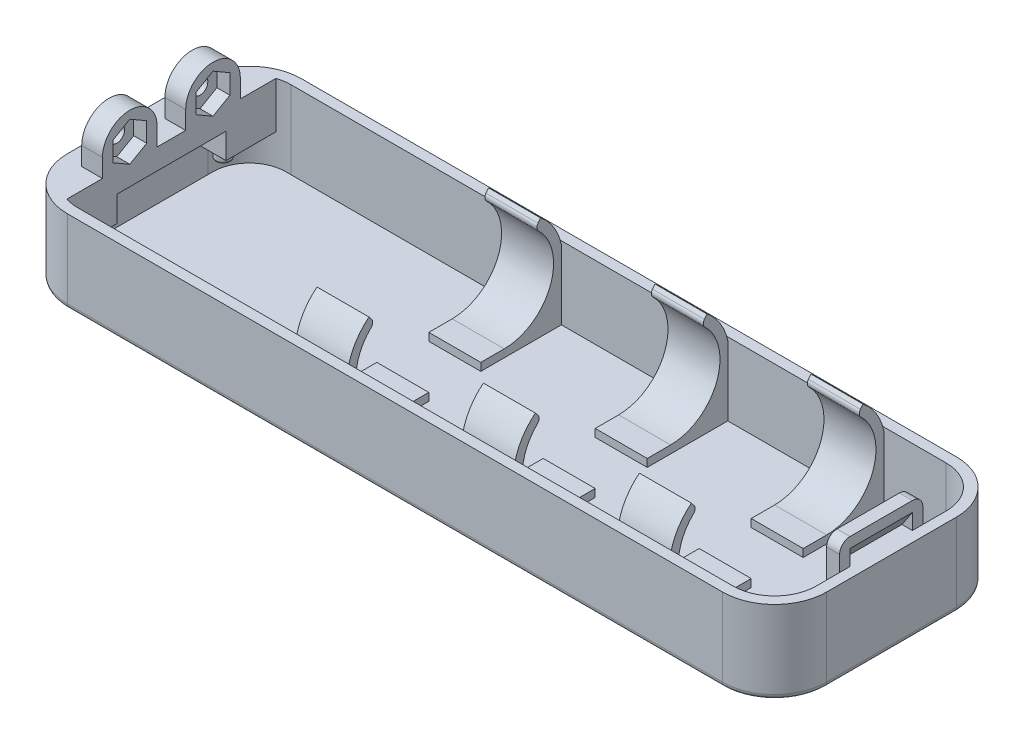
SolidWorks part; units mm, degrees
ref_plane "Front Plane" through (0, 0, 0) normal (0, 0, 1) x (1, 0, 0)
ref_plane "Top Plane" through (0, 0, 0) normal (0, 1, 0) x (1, 0, 0)
ref_plane "Right Plane" through (0, 0, 0) normal (1, 0, 0) x (0, 0, -1)
sketch "Sketch1" plane through (0, 0, 0) normal (0, 1, 0) x (1, 0, 0)
  line L1 (-10, 0) -> (-136, 0)
  line L2 (0, -10) -> (0, -35)
  line L3 (-10, -45) -> (-136, -45)
  line L4 (-146, -10) -> (-146, -35)
  arc A0 (-10, 0) -> (0, -10) centre (-10, -10) cw
  arc A1 (-10, -45) -> (0, -35) centre (-10, -35) ccw
  arc A2 (-146, -35) -> (-136, -45) centre (-136, -35) ccw
  arc A3 (-146, -10) -> (-136, 0) centre (-136, -10) cw
  point P7 (0, 0)
  point P10 (0, -45)
  point P15 (-146, 0)
  dimension "D3" = 10
  dimension "D1" = 146
  dimension "D2" = 45
extrude "Boss-Extrude1" add sketch "Sketch1" along normal blind 2
sketch "Sketch2" plane through (0, 2, 0) normal (0, 1, 0) x (1, 0, 0)
  line L4 (-10, 0) -> (-136, 0)
  line L5 (-146, -10) -> (-146, -35)
  line L6 (-136, -45) -> (-10, -45)
  line L7 (0, -35) -> (0, -10)
  line L8 (-10, 0) -> (-136, 0)
  line L9 (-146, -10) -> (-146, -35)
  line L10 (-136, -45) -> (-10, -45)
  line L11 (0, -35) -> (0, -10)
  line L20 (-10, -2) -> (-136, -2)
  line L21 (-144, -10) -> (-144, -35)
  line L22 (-136, -43) -> (-10, -43)
  line L23 (-2, -35) -> (-2, -10)
  line L24 (-10, -2) -> (-136, -2)
  line L25 (-144, -10) -> (-144, -35)
  line L26 (-136, -43) -> (-10, -43)
  line L27 (-2, -35) -> (-2, -10)
  arc A4 (0, -10) -> (-10, 0) centre (-10, -10) ccw
  arc A5 (-136, 0) -> (-146, -10) centre (-136, -10) ccw
  arc A6 (-146, -35) -> (-136, -45) centre (-136, -35) ccw
  arc A7 (-10, -45) -> (0, -35) centre (-10, -35) ccw
  arc A8 (0, -10) -> (-10, 0) centre (-10, -10) ccw
  arc A9 (-136, 0) -> (-146, -10) centre (-136, -10) ccw
  arc A10 (-146, -35) -> (-136, -45) centre (-136, -35) ccw
  arc A11 (-10, -45) -> (0, -35) centre (-10, -35) ccw
  arc A20 (-2, -10) -> (-10, -2) centre (-10, -10) ccw
  arc A21 (-136, -2) -> (-144, -10) centre (-136, -10) ccw
  arc A22 (-144, -35) -> (-136, -43) centre (-136, -35) ccw
  arc A23 (-10, -43) -> (-2, -35) centre (-10, -35) ccw
  arc A24 (-2, -10) -> (-10, -2) centre (-10, -10) ccw
  arc A25 (-136, -2) -> (-144, -10) centre (-136, -10) ccw
  arc A26 (-144, -35) -> (-136, -43) centre (-136, -35) ccw
  arc A27 (-10, -43) -> (-2, -35) centre (-10, -35) ccw
  dimension "D1" = 0
  dimension "D2" = 2
extrude "Boss-Extrude2" add sketch "Sketch2" along normal blind 14
fillet "Fillet1" radius 1 8 edges at (-73, 0, 0) (-143.0711, 0, 2.9289) (-146, 0, 22.5) (-143.0711, 0, 42.0711) (-73, 0, 45) (-2.9289, 0, 42.0711) (0, 0, 22.5) (-2.9289, 0, 2.9289)
sketch "Sketch3" plane through (0, 2, 0) normal (0, 1, 0) x (1, 0, 0)
  line L0 (-124, -2) -> (-124, -43)
  line L1 (-114, -2) -> (-114, -43)
  line L2 (-32, -2) -> (-32, -43)
  line L3 (-22, -2) -> (-22, -43)
  line L4 (-2, -35) -> (-2, -10)
  line L5 (-10, -2) -> (-136, -2)
  line L6 (-144, -10) -> (-144, -35)
  line L7 (-136, -43) -> (-10, -43)
  line L8 (-2, -35) -> (-2, -10)
  line L9 (-10, -2) -> (-136, -2)
  line L10 (-144, -10) -> (-144, -35)
  line L11 (-136, -43) -> (-10, -43)
  line L12 (-52, -43) -> (-52, -2)
  line L13 (-62, -43) -> (-62, -2)
  line L14 (-84, -43) -> (-84, -2)
  line L15 (-94, -43) -> (-94, -2)
  arc A4 (-2, -10) -> (-10, -2) centre (-10, -10) ccw
  arc A5 (-136, -2) -> (-144, -10) centre (-136, -10) ccw
  arc A6 (-144, -35) -> (-136, -43) centre (-136, -35) ccw
  arc A7 (-10, -43) -> (-2, -35) centre (-10, -35) ccw
  arc A8 (-2, -10) -> (-10, -2) centre (-10, -10) ccw
  arc A9 (-136, -2) -> (-144, -10) centre (-136, -10) ccw
  arc A10 (-144, -35) -> (-136, -43) centre (-136, -35) ccw
  arc A11 (-10, -43) -> (-2, -35) centre (-10, -35) ccw
  line M15 (-10, -2) -> (-136, -2)
  line M19 (-136, -43) -> (-10, -43)
  dimension "D2" = 10
  dimension "D3" = 10
  dimension "D5" = 20
  dimension "D6" = 20
  dimension "D4" = 10
  dimension "D7" = 10
  dimension "D8" = 20
  dimension "D9" = 20
extrude "Boss-Extrude3" add sketch "Sketch3" along normal blind 25 contours L13 L11 L12 L9 | L15 L11 L14 L9 | L3 L2 M15 M19 region at (-89, 2, 22.5) region at (-57, 2, 22.5) region at (-27, 2, 22.5)
ref_plane "Plane3" through (0, 12, 0) normal (0, 1, 0) x (1, 0, 0)
sketch "Sketch4" plane through (-22, 0, 0) normal (-1, 0, 0) x (0, 0, 1)
  line L2 (13, 13) -> (32, 13) construction
  line L3 (13, 22.5) -> (32, 22.5)
  line L4 (27.5, 3.5) -> (27.5, 2)
  line L5 (17.5, 3.5) -> (17.5, 2)
  line L8 (2, 3.5) -> (43, 3.5)
  line L9 (43, 3.5) -> (43, 15.3585)
  line L10 (43, 27) -> (2, 27)
  line L11 (2, 15.3585) -> (2, 3.5)
  line L12 (13, 3.5) -> (32, 3.5)
  line L13 (6, 21.807) -> (7.0889, 20.437)
  line L16 (43, 15.3585) -> (43, 27)
  line L19 (2, 27) -> (2, 15.3585)
  line L20 (39, 21.807) -> (37.9111, 20.437)
  line L21 (2, 2) -> (43, 2)
  line L22 (43, 2) -> (43, 16)
  line L23 (43, 16) -> (43, 27)
  line L24 (43, 27) -> (2, 27)
  line L25 (2, 27) -> (2, 16)
  line L26 (2, 16) -> (2, 2)
  line L27 (2, 2) -> (43, 2)
  line L28 (43, 2) -> (43, 16)
  line L29 (43, 16) -> (43, 27)
  line L30 (43, 27) -> (2, 27)
  line L31 (2, 27) -> (2, 16)
  line L32 (2, 16) -> (2, 2)
  arc A0 (13, 22.5) -> (13, 3.5) centre (13, 13) ccw
  arc A1 (32, 3.5) -> (32, 22.5) centre (32, 13) ccw
  arc A2 (2, 15.3585) -> (6, 21.807) centre (13, 13) cw
  arc A3 (43, 15.3585) -> (39, 21.807) centre (32, 13) ccw
  point P4 (22.5, 27)
  point P5 (22.5, 13)
  point P10 (22.5, 22.5)
  point P31 (22.5, 3.5)
  line M41 (43, 2) -> (2, 2)
  line M42 (2, 2) -> (2, 16)
  line M43 (2, 16) -> (2, 27)
  line M44 (2, 27) -> (43, 27)
  line M45 (43, 27) -> (43, 16)
  line M46 (43, 16) -> (43, 2)
  dimension "D2" = 19
  dimension "D3" = 19
  dimension "D4" = 4
  dimension "D5" = 4
  dimension "D6" = 1.5
  dimension "D7" = 1.75
  dimension "D8" = 10
  dimension "D9" = 5
sketch "Sketch7" plane through (0, 12, 0) normal (0, 1, 0) x (1, 0, 0)
  line L2 (-144, -10) -> (-144, -35)
  line L4 (-138.5, -2.4007) -> (-138.5, -42.5993)
  arc A0 (-136, -2) -> (-144, -10) centre (-136, -10) ccw construction
  arc A1 (-144, -35) -> (-136, -43) centre (-136, -35) ccw construction
  arc A2 (-136, -2) -> (-144, -10) centre (-136, -10) ccw
  arc A3 (-144, -35) -> (-136, -43) centre (-136, -35) ccw
  dimension "D3" = 5.5
extrude "Boss-Extrude5" add sketch "Sketch7" along normal offset from surface (12.75 mm away) 8.75 contours L4 region at (-141.1056, 12, 22.5) up to face at (-73, 16, 22.5) offset beyond the face yes
sketch "Sketch8" plane through (-138.5, 0, 0) normal (1, 0, 0) x (0, 0, -1)
  line L1 (-14.5, 23.25) -> (-17.75, 21.3736)
  line L2 (-17.75, 21.3736) -> (-17.75, 17.6208)
  line L3 (-17.75, 17.6208) -> (-14.5, 15.7444)
  line L4 (-14.5, 15.7444) -> (-11.25, 17.6208)
  line L5 (-11.25, 17.6208) -> (-11.25, 21.3736)
  line L6 (-11.25, 21.3736) -> (-14.5, 23.25)
  line L7 (-30.5, 23.25) -> (-33.75, 21.3736)
  line L8 (-33.75, 21.3736) -> (-33.75, 17.6208)
  line L9 (-33.75, 17.6208) -> (-30.5, 15.7444)
  line L10 (-30.5, 15.7444) -> (-27.25, 17.6208)
  line L11 (-27.25, 17.6208) -> (-27.25, 21.3736)
  line L12 (-27.25, 21.3736) -> (-30.5, 23.25)
  line L14 (-27.25, 17.6208) -> (-17.75, 17.6208)
  line L19 (-42.5993, 16) -> (-42.5993, 12)
  line L22 (-2.4007, 16) -> (-2.4007, 24.75)
  line L23 (-2.4007, 24.75) -> (-42.5993, 24.75)
  line L24 (-42.5993, 24.75) -> (-42.5993, 16)
  line L25 (-42.5993, 12) -> (-2.4007, 12)
  line L26 (-42.5993, 16) -> (-42.5993, 12)
  line L27 (-42.5993, 12) -> (-2.4007, 12)
  line L28 (-2.4007, 16) -> (-2.4007, 24.75)
  line L29 (-2.4007, 24.75) -> (-42.5993, 24.75)
  line L30 (-42.5993, 24.75) -> (-42.5993, 16)
  line L32 (-2.4007, 12) -> (-2.4007, 16)
  line L33 (-2.4007, 12) -> (-2.4007, 16)
  circle A0 centre (-14.5, 19.4972) radius 3.25 construction
  circle A1 centre (-30.5, 19.4972) radius 3.25 construction
  dimension "D1" = 6.5
  dimension "D2" = 6.5
  dimension "D3" = 16
  dimension "D4" = 0
  dimension "D5" = 1.5
extrude "Cut-Extrude3" cut sketch "Sketch8" against normal blind 2.5 contours L11 L12 L7 L8 L9 L10 | L5 L6 L1 L2 L3 L4 region at (-138.5, 19.4972, 14.5) region at (-138.5, 19.4972, 30.5)
sketch "Sketch9" plane through (-144, 0, 0) normal (1, 0, 0) x (0, 0, -1)
  line L0 (-35, 24.75) -> (-42.5993, 24.75) construction
  line L1 (-10, 24.75) -> (-35, 24.75) construction
  line L2 (-10, 24.75) -> (-35, 24.75)
  line L3 (-2.4007, 24.75) -> (-10, 24.75) construction
  line L4 (-35, 24.75) -> (-42.5993, 24.75)
  line L5 (-2.4007, 24.75) -> (-10, 24.75)
  line L9 (-2.4007, 16) -> (-2.4007, 12) construction
  line L10 (-2.4007, 16) -> (-2.4007, 12)
  line L11 (-2.4007, 16) -> (-42.5993, 16)
  line L24 (-33.75, 19.4972) -> (-27.25, 19.4972)
  line L25 (-17.75, 19.4972) -> (-11.25, 19.4972)
  line L26 (-19.7528, 19.4972) -> (-19.7528, 16)
  line L27 (-42.5993, 16) -> (-42.5993, 12) construction
  line L28 (-25.2472, 19.4972) -> (-25.2472, 16)
  line L29 (-35.7528, 19.4972) -> (-35.7528, 14)
  line L30 (-9.2472, 19.4972) -> (-9.2472, 14)
  line L31 (-42.5993, 16) -> (-42.5993, 12)
  line L32 (-10, 16) -> (-35, 16) construction
  line L35 (-10, 16) -> (-35, 16)
  line L39 (-42.5993, 24.75) -> (-42.5993, 16)
  line L40 (-2.4007, 24.75) -> (-2.4007, 16)
  line L42 (-27.25, 17.6208) -> (-27.25, 21.3736) construction
  line L43 (-27.25, 21.3736) -> (-30.5, 23.25) construction
  line L44 (-30.5, 23.25) -> (-33.75, 21.3736) construction
  line L45 (-33.75, 21.3736) -> (-33.75, 17.6208) construction
  line L46 (-33.75, 17.6208) -> (-30.5, 15.7444) construction
  line L47 (-30.5, 15.7444) -> (-27.25, 17.6208) construction
  line L48 (-11.25, 17.6208) -> (-11.25, 21.3736) construction
  line L49 (-11.25, 21.3736) -> (-14.5, 23.25) construction
  line L50 (-14.5, 23.25) -> (-17.75, 21.3736) construction
  line L51 (-17.75, 21.3736) -> (-17.75, 17.6208) construction
  line L52 (-17.75, 17.6208) -> (-14.5, 15.7444) construction
  line L53 (-14.5, 15.7444) -> (-11.25, 17.6208) construction
  line L54 (-27.25, 17.6208) -> (-27.25, 21.3736)
  line L55 (-27.25, 21.3736) -> (-30.5, 23.25)
  line L56 (-30.5, 23.25) -> (-33.75, 21.3736)
  line L57 (-33.75, 21.3736) -> (-33.75, 17.6208)
  line L58 (-33.75, 17.6208) -> (-30.5, 15.7444)
  line L59 (-30.5, 15.7444) -> (-27.25, 17.6208)
  line L60 (-11.25, 17.6208) -> (-11.25, 21.3736)
  line L61 (-11.25, 21.3736) -> (-14.5, 23.25)
  line L62 (-14.5, 23.25) -> (-17.75, 21.3736)
  line L63 (-17.75, 21.3736) -> (-17.75, 17.6208)
  line L64 (-17.75, 17.6208) -> (-14.5, 15.7444)
  line L65 (-14.5, 15.7444) -> (-11.25, 17.6208)
  circle A0 centre (-30.5, 19.4972) radius 1.5
  circle A1 centre (-14.5, 19.4972) radius 1.5
  circle A2 centre (-14.5, 19.4972) radius 5.2528
  circle A3 centre (-30.5, 19.4972) radius 5.2528
  line M89 (-35, 24.75) -> (-10, 24.75)
  line M110 (-35, 16) -> (-35, 24.75)
  line M111 (-10, 24.75) -> (-10, 16)
  dimension "D1" = 3
extrude "Cut-Extrude5" cut sketch "Sketch9" along normal up to surface (5.5 mm away) contours L30 A2 L2 L5 L40 L11 | L28 A3 L2 A2 L26 L11 | L2 A3 L29 L11 L39 L4 | A0 L24 | A0 L24 | A1 L25 | A1 L25 | A2 L2 M111 | A3 M89 M110 region at (-144, 24.034, 11.0634) region at (-144, 20.4824, 5.9788) region at (-144, 21.0078, 22.5) region at (-144, 24.034, 33.9366) region at (-144, 20.4824, 39.0212) region at (-144, 20.1338, 14.5) region at (-144, 18.8606, 14.5) region at (-144, 18.8606, 30.5) region at (-144, 20.1338, 30.5) up to face at (-138.5, 19.4972, 30.5)
sketch "Sketch10" plane through (0, 2, 0) normal (0, 1, 0) x (1, 0, 0)
  line L0 (-2, -35) -> (-2, -10) construction
  line L1 (-2, -35) -> (-2, -10)
  line L2 (-2, -14.5) -> (-4.5, -14.5)
  line L3 (-4.5, -14.5) -> (-4.5, -30.5)
  line L4 (-4.5, -30.5) -> (-2, -30.5)
  line L5 (-2, -14.5) -> (-2, -30.5)
  point P4 (-4.5, -22.5)
  point P7 (-2, -22.5)
  dimension "D1" = 16
  dimension "D2" = 2.5
extrude "Boss-Extrude6" add sketch "Sketch10" along normal offset from surface (19 mm away) 5 contours L3 L4 L1 L2 region at (-3.25, 2, 22.5) up to face at (-73, 16, 22.5) offset beyond the face yes
ref_plane "Plane1" through (0, 0, 16.5) normal (0, 0, -1) x (-1, 0, 0)
sketch "Sketch11" plane through (0, 0, 16.5) normal (0, 0, -1) x (-1, 0, 0)
  line L0 (4.5, 21) -> (4.5, 2) construction
  line L1 (2, 21) -> (4.5, 21) construction
  line L2 (2, 21) -> (2, 16) construction
  line L3 (4.5, 21) -> (4.5, 2)
  line L4 (2, 21) -> (4.5, 21)
  line L5 (2, 21) -> (2, 16)
  line L6 (2, 19) -> (4, 16)
  line L7 (4, 16) -> (2, 16)
  line L8 (2, 19) -> (2, 16)
  dimension "D1" = 2
  dimension "D2" = 3
extrude "Cut-Extrude6" cut sketch "Sketch11" against normal offset from surface (12 mm away) 2 contours L8 L6 L7 up to face at (-3, 12.4, 30.5)
fillet "Fillet2" radius 2 2 edges at (-3.25, 21, 14.5) (-3.25, 21, 30.5)
ref_plane "Plane2" through (0, 24.75, 0) normal (0, 1, 0) x (1, 0, 0)
sketch "Sketch12" plane through (0, 24.75, 0) normal (0, 1, 0) x (1, 0, 0)
  line L0 (-143.9645, -35.7528) -> (-138.5, -35.7528) construction
  line L1 (-138.5, -35.7528) -> (-138.5, -25.2472) construction
  line L2 (-138.5, -25.2472) -> (-144, -25.2472) construction
  line L3 (-144, -25.2472) -> (-144, -35) construction
  line L4 (-144, -10) -> (-144, -19.7528) construction
  line L5 (-144, -19.7528) -> (-138.5, -19.7528) construction
  line L6 (-138.5, -19.7528) -> (-138.5, -9.2472) construction
  line L7 (-138.5, -9.2472) -> (-143.9645, -9.2472) construction
  line L8 (-143.9645, -35.7528) -> (-138.5, -35.7528)
  line L9 (-138.5, -35.7528) -> (-138.5, -25.2472)
  line L10 (-138.5, -25.2472) -> (-144, -25.2472)
  line L11 (-144, -25.2472) -> (-144, -35)
  line L12 (-144, -10) -> (-144, -19.7528)
  line L13 (-144, -19.7528) -> (-138.5, -19.7528)
  line L14 (-138.5, -19.7528) -> (-138.5, -9.2472)
  line L15 (-138.5, -9.2472) -> (-143.9645, -9.2472)
  line L16 (-142.5, -9.2472) -> (-142.5, -19.7528)
  line L17 (-142.5, -25.2472) -> (-142.5, -35.7528)
  arc A0 (-144, -35) -> (-143.9645, -35.7528) centre (-136, -35) ccw construction
  arc A1 (-143.9645, -9.2472) -> (-144, -10) centre (-136, -10) ccw construction
  arc A2 (-144, -35) -> (-143.9645, -35.7528) centre (-136, -35) ccw
  arc A3 (-143.9645, -9.2472) -> (-144, -10) centre (-136, -10) ccw
  dimension "D1" = 1.5
extrude "Cut-Extrude7" cut sketch "Sketch12" against normal up to surface (8.75 mm away) contours L15 A3 L12 L13 L16 | L11 A2 L8 L17 L10 region at (-143.2496, 24.75, 30.4971) region at (-143.2496, 24.75, 14.5029) up to face at (-73, 16, 22.5)
extrude "Cut-Extrude13" cut sketch "Sketch4" along normal blind 84 contours A1 L8 A0 L3 | A3 L20 A1 L3 A0 L13 A2 M46 M42 M43 M44 M45 | L5 L8 L4 M41 region at (-22, 24.1296, 22.5) region at (-22, 13, 22.5) region at (-22, 2.75, 22.5)
sketch "Sketch15" plane through (0, 0, 0) normal (0, -1, 0) x (1, 0, 0)
  line L0 (-94, 2) -> (-136, 2) construction
  line L1 (-144, 10) -> (-144, 35) construction
  line L2 (-136, 43) -> (-94, 43) construction
  line L3 (-94, 2) -> (-136, 2)
  line L4 (-144, 10) -> (-144, 35)
  line L5 (-136, 43) -> (-94, 43)
  line L6 (-94, 2) -> (-94, 43)
  line L7 (-95, 3) -> (-136, 3)
  line L8 (-143, 10) -> (-143, 35)
  line L9 (-136, 42) -> (-95, 42)
  line L10 (-95, 3) -> (-95, 42)
  line L11 (-95, 3) -> (-94, 3)
  line L12 (-95, 42) -> (-94, 42)
  arc A0 (-144, 10) -> (-136, 2) centre (-136, 10) ccw construction
  arc A1 (-136, 43) -> (-144, 35) centre (-136, 35) ccw construction
  arc A2 (-144, 10) -> (-136, 2) centre (-136, 10) ccw
  arc A3 (-136, 43) -> (-144, 35) centre (-136, 35) ccw
  arc A4 (-143, 10) -> (-136, 3) centre (-136, 10) ccw
  arc A5 (-136, 42) -> (-143, 35) centre (-136, 35) ccw
  dimension "D1" = 50
  dimension "D2" = 1
extrude "Cut-Extrude15" cut sketch "Sketch15" against normal up to surface (2 mm away) contours A5 L9 L12 L6 L5 A3 L4 A2 L3 L11 L7 A4 L8 region at (-115, 0, 2.6466) up to face at (-55.0278, 2, 22.5)
sketch "Sketch16" plane through (0, 12, 0) normal (0, -1, 0) x (1, 0, 0)
  line L0 (-144, 33) -> (-138.5, 33)
  line L1 (-144, 12) -> (-138.5, 12)
  line L2 (-144, 35) -> (-144, 10)
  line L12 (-144, 35) -> (-144, 10)
  line L14 (-138.5, 2.4007) -> (-138.5, 42.5993)
  line L15 (-138.5, 2.4007) -> (-138.5, 42.5993)
  arc A2 (-144, 10) -> (-138.5, 2.4007) centre (-136, 10) ccw
  arc A3 (-138.5, 42.5993) -> (-144, 35) centre (-136, 35) ccw
  arc A5 (-138.5, 42.5993) -> (-144, 35) centre (-136, 35) ccw
  arc A7 (-144, 10) -> (-138.5, 2.4007) centre (-136, 10) ccw
  line M7 (-144, 35) -> (-144, 10)
  arc M8 (-144, 10) -> (-138.5, 2.4007) centre (-136, 10) ccw
  line M9 (-138.5, 2.4007) -> (-138.5, 42.5993)
  arc M10 (-138.5, 42.5993) -> (-144, 35) centre (-136, 35) ccw
  dimension "D2" = 21
  dimension "D1" = 0
extrude "Boss-Extrude7" add sketch "Sketch16" along normal blind 4.9 contours L0 M7 M9 M10 | L1 M7 M8 M9 region at (-140.9052, 12, 36.9779) region at (-140.9052, 12, 8.0221)
sketch "Sketch17" plane through (0, 7.1, 0) normal (0, -1, 0) x (1, 0, 0)
  line L0 (-144, 12) -> (-144, 33) construction
  line L1 (-144, 12) -> (-144, 33)
  line L2 (-144, 12) -> (-138.5, 12) construction
  line L3 (-144, 12) -> (-138.5, 12)
  circle A0 centre (-141.25, 35.2) radius 1.4
  circle A1 centre (-141.25, 9.8) radius 1.4
  point P9 (-144, 22.5)
  dimension "D2" = 2.8
  dimension "D1" = 25.4
  dimension "D3" = 12.7
  dimension "D4" = 5.5
  dimension "D5" = 2.75
extrude "Boss-Extrude8" add sketch "Sketch17" along normal blind 2 contours A0 | A1
fillet "Fillet3" radius 0.25 2 edges at (-141.25, 5.1, 33.8) (-141.25, 5.1, 8.4)
sketch "Sketch19" plane through (-94, 0, 0) normal (-1, 0, 0) x (0, 0, 1)
  line L0 (40.0243, 7.9146) -> (42, 5.7253)
  line L1 (42, 5.7253) -> (42, 2.5)
  line L2 (42, 2.5) -> (40, 2.5)
  line L3 (40, 2.5) -> (40, 4.9563)
  line L4 (40, 4.9563) -> (38.7624, 6.3277)
  line L5 (39, 21.807) -> (37.9111, 20.437)
  line L7 (39, 21.807) -> (37.9111, 20.437)
  line L9 (32, 3.5) -> (27.5, 3.5)
  line L22 (27.5, 3.5) -> (27.5, 2)
  line L23 (32, 3.5) -> (27.5, 3.5)
  line L24 (27.5, 2) -> (42, 2)
  line L28 (27.5, 2) -> (42, 2)
  line L32 (27.5, 3.5) -> (27.5, 2)
  line L34 (42, 2) -> (42, 0)
  line L36 (42, 2) -> (42, 0)
  line L40 (42, 0) -> (43, 0)
  line L41 (42, 0) -> (43, 0)
  line L42 (43, 0) -> (43, 15.3585)
  line L43 (43, 0) -> (43, 15.3585)
  arc A3 (32, 3.5) -> (37.9111, 20.437) centre (32, 13) ccw
  arc A5 (32, 3.5) -> (37.9111, 20.437) centre (32, 13) ccw
  arc A9 (43, 15.3585) -> (39, 21.807) centre (32, 13) ccw
  arc A10 (43, 15.3585) -> (39, 21.807) centre (32, 13) ccw
  arc M15 (37.9111, 20.437) -> (32, 3.5) centre (32, 13) cw
  dimension "D2" = 2
  dimension "D3" = 2
extrude "Cut-Extrude16" cut sketch "Sketch19" against normal up to surface (42 mm away) contours L4 L3 L2 L1 L0 M15 region at (-94, 4.9886, 40.6943) up to face at (-52, 9.5501, 36.6407)
fillet "Fillet4" radius 1 6 edges at (-27, 20.437, 7.0889) (-57, 20.437, 7.0889) (-89, 20.437, 7.0889) (-89, 20.437, 37.9111) (-27, 20.437, 37.9111) (-57, 20.437, 37.9111)
equation "\"D3@Sketch3\"=\"D2@Sketch3\""
equation "\"D6@Sketch3\"=\"D5@Sketch3\""
equation "\"D4@Sketch3\"=\"D2@Sketch3\""
equation "\"D7@Sketch3\"=\"D2@Sketch3\""
equation "\"D8@Sketch3\"=\"D5@Sketch3\""
equation "\"D9@Sketch3\"=\"D5@Sketch3\""
equation "\"D5@Sketch4\"=\"D4@Sketch4\""
equation "\"D3@Sketch17\"=\"D1@Sketch17\"/2"
equation "\"D3@Sketch19\"=\"D2@Sketch19\""
